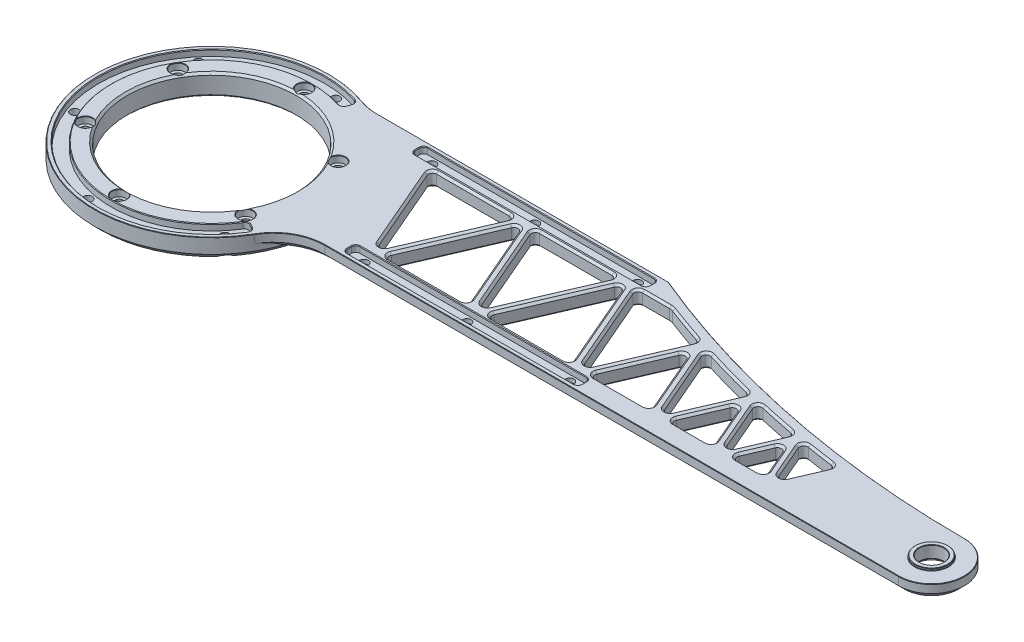
SolidWorks part; units mm, degrees
note: The reader was unsure of these and kept them because the rebuilt part matched: shared geometry of "스케치1<37>", "스케치1<38>".
material "6061-T6 (SS)"
ref_plane "정면" through (0, 0, 0) normal (0, 0, 1) x (1, 0, 0)
ref_plane "윗면" through (0, 0, 0) normal (0, 1, 0) x (1, 0, 0)
ref_plane "우측면" through (0, 0, 0) normal (1, 0, 0) x (0, 0, -1)
sketch "스케치1" plane through (0, 0, 0) normal (0, 1, 0) x (1, 0, 0)
  line L0 (0, 0) -> (350, 0) construction
  line L1 (0, 45) -> (0, 0) construction
  line L2 (0, 0) -> (38.9711, 22.5) construction
  line L3 (71.0141, -16) -> (350, -16)
  line L4 (350, -14) -> (71.0141, -14)
  line L5 (350, 32) -> (350, 40) construction
  line L6 (350, 16) -> (46.3141, 16) construction
  line L7 (350, 40) -> (40.6079, 40) construction
  line L8 (169.6004, 50) -> (28.1957, 50)
  line L9 (170, 52) -> (28.1957, 52)
  line L10 (85, -11) -> (185, -11) construction
  line L11 (0, 32) -> (350, 32) construction
  line L12 (0, 45) -> (0, 0) construction
  line L13 (0, 0) -> (-39.8343, 33.425) construction
  line L14 (-39.8343, 33.425) -> (0, 0) construction
  line L15 (0, 0) -> (-52, 0) construction
  line L16 (60, 47) -> (160, 47) construction
  line L17 (-39.8343, 33.425) -> (0, 0) construction
  line L18 (0, 0) -> (9.0297, 51.21) construction
  circle A18 centre (0, 0) radius 41
  circle A19 centre (350, 0) radius 6
  circle A25 centre (0, 0) radius 45
  circle A26 centre (0, 0) radius 49
  circle A28 centre (0, 45) radius 2.1
  circle A33 centre (0, 45) radius 3.5
  circle A34 centre (38.9711, 22.5) radius 2.1
  circle A36 centre (38.9711, 22.5) radius 3.5
  circle A37 centre (38.9711, -22.5) radius 2.1
  circle A38 centre (38.9711, -22.5) radius 3.5
  circle A40 centre (0, -45) radius 2.1
  circle A41 centre (0, -45) radius 3.5
  circle A42 centre (-38.9711, -22.5) radius 2.1
  circle A44 centre (-38.9711, -22.5) radius 3.5
  circle A45 centre (-38.9711, 22.5) radius 2.1
  circle A46 centre (-38.9711, 22.5) radius 3.5
  circle A48 centre (350, 0) radius 14
  arc A49 (322.2872, -16) -> (322.7607, 16.7934) centre (350, 0) ccw
  circle A50 centre (0, 0) radius 32
  arc A52 (350, -16) -> (342.254, -14) centre (350, 0) ccw
  arc A60 (170, 52) -> (350, 16) centre (350, 484) ccw
  arc A61 (169.6004, 50) -> (350, 14) centre (350, 484) ccw
  arc A75 (19.5995, 53.5244) -> (49.3634, -28.5) centre (0, 0) ccw
  arc A110 (71.0141, -16) -> (49.3634, -28.5) centre (71.0141, -41) ccw
  arc A111 (71.0141, -14) -> (47.6314, -27.5) centre (71.0141, -41) ccw
  circle A114 centre (0, 0) radius 55
  circle A130 centre (0, 0) radius 52
  circle A131 centre (60, 47) radius 2.1
  circle A142 centre (-39.8343, 33.425) radius 2.1
  circle A143 centre (9.0297, 51.21) radius 2.1
  circle A145 centre (39.8343, -33.425) radius 2.1
  circle A146 centre (-9.0297, -51.21) radius 2.1
  arc A147 (19.5995, 53.5244) -> (28.1957, 52) centre (28.1957, 77) ccw
  arc A148 (18.9118, 51.6463) -> (28.1957, 50) centre (28.1957, 77) ccw
  arc A149 (53.0537, -20.84) -> (27.3679, 50) centre (0, 0) ccw
  circle A152 centre (85, -11) radius 2.1
  circle A161 centre (135, -11) radius 2.1
  circle A165 centre (185, -11) radius 2.1
  circle A168 centre (110, 47) radius 2.1
  circle A172 centre (235, -11) radius 2.1 [skipped]
  circle A177 centre (160, 47) radius 2.1
  circle A180 centre (0, 0) radius 57
  circle A181 centre (-48.864, -17.785) radius 2.1
  circle A182 centre (48.864, 17.785) radius 2.1 [skipped]
  point P29 (0, 0)
  point P57 (-0.5, 0.2887)
  point P59 (0, 0)
  point P73 (0, 0)
  point P120 (0, 0)
  point P168 (0, 0)
  point P170 (0, 0)
  point P171 (0, 0)
  dimension "D2" = 82
  dimension "D3" = 90
  dimension "D4" = 98
  dimension "D7" = 7
  dimension "D8" = 60
  dimension "D10" = 28
  dimension "D11" = 64
  dimension "D12" = 64
  dimension "D13" = 32
  dimension "D14" = 60
  dimension "D19" = 50
  dimension "D21" = 50
  dimension "D17" = 180
  dimension "D20" = 3
  dimension "D22" = 8
  dimension "D23" = 2
  dimension "D25" = 50
  dimension "D26" = 4.2
  dimension "D28" = 85
  dimension "D32" = 3
  dimension "D33" = 50
  dimension "D35" = 4
  dimension "D5" = 114
  dimension "D6" = 4.2
  dimension "D9" = 12
  dimension "D18" = 6
  dimension "D16" = 104
  dimension "D27" = 4.2
  dimension "D37" = 25
  dimension "D15" = 4.2
  dimension "D1" = 350
  dimension "D34" = 6
  dimension "D38" = 50
  dimension "D24" = 10
  dimension "D30" = 3
sketch "스케치2" plane through (0, 0, 0) normal (0, 1, 0) x (1, 0, 0)
  circle A10 centre (350, 0) radius 6.25
  circle A11 centre (382.6753, 12.5429) radius 10
  arc A12 (390.9123, -1.174) -> (378.5037, 27.9895) centre (382.6753, 12.5429) ccw
  arc A13 (231.9844, -40.1605) -> (80.8156, -91.5048) centre (227.4834, -275.1173) ccw
  arc A14 (357.0381, -19.254) -> (358.9138, -18.4606) centre (350, 0) ccw
  arc A15 (358.9138, -18.4606) -> (390.9123, -1.174) centre (184.9867, 341.7468) ccw
  arc A16 (231.9844, -40.1605) -> (357.0381, -19.254) centre (238.5923, 304.7763) ccw
  arc A17 (378.5037, 27.9895) -> (343.7427, 16.8774) centre (482.7931, -358.1759) ccw
  arc A18 (233.0814, -9.5331) -> (343.3893, 16.7421) centre (196.4849, 388.7893) ccw
  arc A19 (233.0814, -9.5331) -> (41.3157, -82.3545) centre (261.5552, -373.4208) ccw
sketch "스케치3" plane through (0, 0, 0) normal (0, 1, 0) x (1, 0, 0)
  line L0 (350, -2.1721) -> (350, 87.1857) construction
  line L1 (350, 32) -> (0, 32) construction
  line L2 (350, 36) -> (-50.8808, 36) construction
  line L3 (350, 28) -> (-10.04, 28) construction
  circle A0 centre (356.8277, -1.9267) radius 6.25
  circle A1 centre (350, 32) radius 10
  arc A2 (365.7576, 37.7743) -> (333.8887, 36.6981) centre (350, 32) ccw
  arc A3 (345.2, -124.5693) -> (338.96, -284.0977) centre (562.9381, -212.9724) ccw
  arc A4 (377.1409, -4.6879) -> (376.6334, 3.3632) centre (356.8277, -1.9267) ccw
  arc A5 (376.6334, 3.3632) -> (365.7576, 37.7743) centre (-9.8202, -99.853) ccw
  arc A6 (345.2, -124.5693) -> (377.1409, -4.6879) centre (-114.7569, 62.1762) ccw
  arc A7 (333.8887, 36.6981) -> (325.3353, 1.5106) centre (717.8951, -75.28) ccw
  arc A8 (317, -112.5693) -> (332.0008, -0.1718) centre (-67.981, -3.9891) ccw
  arc A9 (317, -112.5693) -> (316.262, -317.6949) centre (666.9225, -216.3924) ccw
  dimension "D1" = 4
  dimension "D2" = 4
extrude "보스-돌출1" add sketch "스케치1" along normal blind 7
extrude "보스-돌출2" add sketch "스케치1<37>" against normal blind 3.2
sketch "스케치1<37>" plane through (0, 0, 0) normal (0, 1, 0) x (1, 0, 0) same geometry as "스케치1"
extrude "컷-돌출1" cut sketch "스케치1<38>" against normal blind 3.2 from surface at 7 contours A25 A33 A28 | A25 A33 A28 | A25 A46 A45 | A25 A46 A45 | A25 A44 A42 | A25 A44 A42 | A25 A41 A40 | A25 A41 A40 | A25 A38 A37 | A25 A38 A37 | A25 A36 A34 | A25 A36 A34
sketch "스케치1<38>" plane through (0, 0, 0) normal (0, 1, 0) x (1, 0, 0) same geometry as "스케치1"
sketch "스케치5" plane through (0, -3.2, 0) normal (0, -1, 0) x (1, 0, 0)
  line L0 (-9.0297, 51.21) -> (0, 0) construction
  line L1 (0, 0) -> (39.8343, 33.425) construction
  circle A0 centre (-9.0297, 51.21) radius 3.5
  circle A1 centre (39.8343, 33.425) radius 3.5
  circle A3 centre (9.0297, -51.21) radius 3.5
  circle A4 centre (-39.8343, -33.425) radius 3.5
  circle A5 centre (-48.864, 17.785) radius 3.5
  circle A6 centre (48.864, -17.785) radius 3.5 [skipped]
  point P15 (0, 0)
  dimension "D1" = 7
  dimension "D3" = 60
  dimension "D2" = 6
extrude "컷-돌출2" cut sketch "스케치5" against normal blind 3.2
sketch "스케치4" plane through (0, 7, 0) normal (0, 1, 0) x (1, 0, 0)
  line L0 (0, 0) -> (19.5995, 53.5244) construction
  line L1 (16.8487, 46.0122) -> (18.9118, 51.6463)
  line L2 (0, 0) -> (49.3634, -28.5) construction
  line L3 (47.6314, -27.5) -> (42.4352, -24.5)
  line L4 (55, 44) -> (165, 44)
  line L5 (55, 50) -> (165, 50)
  line L6 (53, 48) -> (53, 46)
  line L7 (167, 48) -> (167, 46)
  line L8 (80, -8) -> (190, -8)
  line L9 (80, -14) -> (190, -14)
  line L10 (78, -10) -> (78, -12)
  line L11 (192, -10) -> (192, -12)
  line L12 (60, 47) -> (160, 47) construction
  line L13 (85, -11) -> (185, -11) construction
  circle A0 centre (0, 0) radius 52
  circle A1 centre (0, 0) radius 55
  circle A2 centre (0, 0) radius 49
  arc A29 (46.5597, -29.2778) -> (45.8667, -26.4811) centre (44.8667, -28.2132) ccw
  arc A32 (44.1333, -25.4804) -> (41.4418, -26.1453) centre (43.1333, -27.2124) ccw
  arc A33 (18.2111, 49.7328) -> (16.9494, 52.3232) centre (16.333, 50.4205) ccw
  arc A34 (15.0313, 46.6375) -> (17.5229, 47.8534) centre (15.6448, 48.5411) ccw
  arc A35 (165, 44) -> (167, 46) centre (165, 46) ccw
  arc A36 (165, 50) -> (167, 48) centre (165, 48) cw
  arc A37 (55, 44) -> (53, 46) centre (55, 46) cw
  arc A38 (55, 50) -> (53, 48) centre (55, 48) ccw
  arc A40 (190, -14) -> (192, -12) centre (190, -12) ccw
  arc A41 (190, -8) -> (192, -10) centre (190, -10) cw
  arc A42 (80, -14) -> (78, -12) centre (80, -12) cw
  arc A43 (80, -8) -> (78, -10) centre (80, -10) ccw
  circle M26 centre (39.8343, -33.425) radius 2.1
  circle M27 centre (-9.0297, -51.21) radius 2.1
  circle M28 centre (-48.864, -17.785) radius 2.1
  circle M29 centre (-39.8343, 33.425) radius 2.1
  circle M30 centre (185, -11) radius 2.1
  circle M31 centre (135, -11) radius 2.1
  circle M32 centre (85, -11) radius 2.1
  circle M40 centre (60, 47) radius 2.1
  circle M41 centre (110, 47) radius 2.1
  circle M42 centre (160, 47) radius 2.1
  dimension "D9" = 2
  dimension "D10" = 3
  dimension "D13" = 7
  dimension "D2" = 3
  dimension "D3" = 3
  dimension "D4" = 2
  dimension "D5" = 2
  dimension "D14" = 2
  dimension "D1" = 3
  dimension "D6" = 3
  dimension "D7" = 7
  dimension "D8" = 7
  dimension "D11" = 3
  dimension "D12" = 7
extrude "컷-돌출3" cut sketch "스케치4" against normal blind 3 contours L1 A33 A1 A29 L3 A0 M26 M27 M28 M29 | A2 A34 L1 A0 L3 A32 M29 M28 M27 M26 | L5 A38 L6 A37 L4 A35 L7 A36 M41 M40 M42 | L8 A43 L10 A42 L9 A40 L11 A41 M31 M32 M30
sketch "스케치6" plane through (0, 7, 0) normal (0, 1, 0) x (1, 0, 0)
  circle A0 centre (350, 0) radius 6
  circle A1 centre (350, 0) radius 8
  dimension "D1" = 12
  dimension "D2" = 16
extrude "보스-돌출3" add sketch "스케치6" along normal blind 1
sketch "스케치7" plane through (0, 0, 0) normal (0, -1, 0) x (1, 0, 0)
  circle A0 centre (85, 11) radius 3.5
  circle A1 centre (135, 11) radius 3.5
  circle A2 centre (185, 11) radius 3.5
  circle A3 centre (160, -47) radius 3.5
  circle A4 centre (110, -47) radius 3.5
  circle A5 centre (60, -47) radius 3.5
  dimension "D1" = 7
extrude "컷-돌출4" cut sketch "스케치7" against normal blind 2
sketch "스케치8" plane through (0, 7, 0) normal (0, 1, 0) x (1, 0, 0)
  line L0 (60, 47) -> (85, -11) construction
  line L1 (85, -11) -> (110, 47) construction
  line L2 (110, 47) -> (135, -11) construction
  line L3 (135, -11) -> (160, 47) construction
  line L4 (160, 47) -> (185, -11) construction
  line L5 (92.373, -6) -> (127.627, -6)
  line L6 (185, -11) -> (204.3845, 33.9721) construction
  line L7 (204.3845, 33.9721) -> (223.769, -11) construction
  line L8 (223.769, -11) -> (238.9504, 24.2207) construction
  line L9 (238.9504, 24.2207) -> (254.1317, -11) construction
  line L10 (254.1317, -11) -> (266.7938, 18.376) construction
  line L11 (65.5364, 39.2083) -> (83.1634, -1.6863)
  line L12 (67.373, 42) -> (102.627, 42)
  line L13 (104.4636, 39.2083) -> (86.8366, -1.6863)
  line L14 (55, 44) -> (165, 44) construction
  line L15 (108.1634, 37.6863) -> (90.5364, -3.2083)
  line L16 (111.8366, 37.6863) -> (129.4636, -3.2083)
  line L17 (80, -8) -> (190, -8) construction
  line L18 (115.5364, 39.2083) -> (133.1634, -1.6863)
  line L19 (117.373, 42) -> (152.627, 42)
  line L20 (154.4636, 39.2083) -> (136.8366, -1.6863)
  line L21 (55, 44) -> (165, 44) construction
  line L22 (158.1634, 37.6863) -> (140.5364, -3.2083)
  line L23 (161.8366, 37.6863) -> (179.4636, -3.2083)
  line L24 (142.373, -6) -> (177.627, -6)
  line L25 (231.142, -6) -> (246.7587, -6)
  line L26 (237.1137, 14.907) -> (229.3054, -3.2083)
  line L27 (165.5364, 39.2083) -> (183.1634, -1.6863)
  line L28 (201.6108, 32.5897) -> (186.8366, -1.6863)
  line L29 (192.373, -6) -> (216.396, -6)
  line L30 (202.5479, 24.6584) -> (190.5364, -3.2083)
  line L31 (206.2212, 24.6584) -> (218.2327, -3.2083)
  line L32 (240.787, 14.907) -> (248.5954, -3.2083)
  line L33 (242.9438, 20.0088) -> (252.2951, -1.6863)
  line L34 (208.6351, 29.1633) -> (221.9324, -1.6863)
  line L35 (236.0469, 22.5374) -> (225.6057, -1.6863)
  line L36 (263.782, 16.4414) -> (255.9684, -1.6863)
  line L37 (152.627, 42) -> (180.6631, 42) construction
  line L38 (180.6631, 42) -> (167.373, 42)
  line L39 (266.7938, 18.376) -> (279.4558, -11) construction
  line L40 (279.4558, -11) -> (290.5551, 14.7503) construction
  line L41 (261.5047, -6) -> (272.0828, -6)
  line L42 (264.9571, 9.0623) -> (259.6681, -3.2083)
  line L43 (268.6304, 9.0623) -> (273.9195, -3.2083)
  line L44 (270.6067, 14.5827) -> (277.6192, -1.6863)
  line L45 (287.4473, 12.5928) -> (281.2925, -1.6863)
  circle A0 centre (350, 484) radius 468
  arc A1 (170, 52) -> (350, 16) centre (350, 484) ccw construction
  circle A2 centre (350, 484) radius 473
  arc A7 (83.1634, -1.6863) -> (86.8366, -1.6863) centre (85, -0.8946) ccw
  arc A8 (104.4636, 39.2083) -> (102.627, 42) centre (102.627, 40) ccw
  arc A9 (65.5364, 39.2083) -> (67.373, 42) centre (67.373, 40) cw
  arc A10 (92.373, -6) -> (90.5364, -3.2083) centre (92.373, -4) cw
  arc A11 (127.627, -6) -> (129.4636, -3.2083) centre (127.627, -4) ccw
  arc A12 (111.8366, 37.6863) -> (108.1634, 37.6863) centre (110, 36.8946) ccw
  arc A13 (136.8366, -1.6863) -> (133.1634, -1.6863) centre (135, -0.8946) cw
  arc A14 (154.4636, 39.2083) -> (152.627, 42) centre (152.627, 40) ccw
  arc A15 (115.5364, 39.2083) -> (117.373, 42) centre (117.373, 40) cw
  arc A16 (177.627, -6) -> (179.4636, -3.2083) centre (177.627, -4) ccw
  arc A17 (142.373, -6) -> (140.5364, -3.2083) centre (142.373, -4) cw
  arc A18 (161.8366, 37.6863) -> (158.1634, 37.6863) centre (160, 36.8946) ccw
  arc A19 (186.8366, -1.6863) -> (183.1634, -1.6863) centre (185, -0.8946) cw
  arc A20 (201.6108, 32.5897) -> (200.4067, 35.2787) centre (199.7741, 33.3813) ccw
  arc A22 (216.396, -6) -> (218.2327, -3.2083) centre (216.396, -4) ccw
  arc A23 (192.373, -6) -> (190.5364, -3.2083) centre (192.373, -4) cw
  arc A24 (206.2212, 24.6584) -> (202.5479, 24.6584) centre (204.3845, 23.8667) ccw
  arc A25 (225.6057, -1.6863) -> (221.9324, -1.6863) centre (223.769, -0.8946) cw
  arc A26 (211.0593, 31.8668) -> (208.6351, 29.1633) centre (210.4718, 29.955) ccw
  arc A27 (236.0469, 22.5374) -> (234.6978, 25.2687) centre (234.2103, 23.329) ccw
  arc A28 (246.7587, -6) -> (248.5954, -3.2083) centre (246.7587, -4) ccw
  arc A29 (231.142, -6) -> (229.3054, -3.2083) centre (231.142, -4) cw
  arc A30 (240.787, 14.907) -> (237.1137, 14.907) centre (238.9504, 14.1154) ccw
  arc A31 (255.9684, -1.6863) -> (252.2951, -1.6863) centre (254.1317, -0.8946) cw
  arc A32 (245.2234, 22.7507) -> (242.9438, 20.0088) centre (244.7804, 20.8004) ccw
  arc A33 (263.782, 16.4414) -> (262.3161, 19.1984) centre (261.9454, 17.2331) ccw
  arc A34 (165.5364, 39.2083) -> (167.373, 42) centre (167.373, 40) cw
  arc A35 (182.4344, 41.6757) -> (180.6631, 42) centre (180.6631, 37) ccw
  arc A36 (272.0828, -6) -> (273.9195, -3.2083) centre (272.0828, -4) ccw
  arc A37 (261.5047, -6) -> (259.6681, -3.2083) centre (261.5047, -4) cw
  arc A38 (268.6304, 9.0623) -> (264.9571, 9.0623) centre (266.7938, 8.2706) ccw
  arc A39 (281.2925, -1.6863) -> (277.6192, -1.6863) centre (279.4558, -0.8946) cw
  arc A40 (272.7699, 17.3475) -> (270.6067, 14.5827) centre (272.4433, 15.3744) ccw
  arc A41 (287.4473, 12.5928) -> (285.8817, 15.366) centre (285.6106, 13.3844) ccw
  dimension "D1" = 5
  dimension "D5" = 2
  dimension "D9" = 2
  dimension "D13" = 2
  dimension "D16" = 2
  dimension "D19" = 2
  dimension "D20" = 4
  dimension "D21" = 2
  dimension "D24" = 2
  dimension "D27" = 2
  dimension "D28" = 4
  dimension "D31" = 2
  dimension "D34" = 2
  dimension "D35" = 4
  dimension "D36" = 10
  dimension "D39" = 2
  dimension "D42" = 2
  dimension "D43" = 4
  dimension "D2" = 2
  dimension "D3" = 2
  dimension "D4" = 2
  dimension "D6" = 2
  dimension "D7" = 2
  dimension "D8" = 2
  dimension "D10" = 2
  dimension "D11" = 2
  dimension "D12" = 2
  dimension "D14" = 2
  dimension "D15" = 2
  dimension "D17" = 2
  dimension "D18" = 2
  dimension "D22" = 2
  dimension "D23" = 2
  dimension "D25" = 2
  dimension "D26" = 2
  dimension "D29" = 2
  dimension "D30" = 2
  dimension "D32" = 2
  dimension "D33" = 2
  dimension "D37" = 2
  dimension "D38" = 2
  dimension "D40" = 2
  dimension "D41" = 2
extrude "컷-돌출5" cut sketch "스케치8" against normal blind 7 contours A9 L11 A7 L13 A8 L12 | L16 A12 L15 A10 L5 A11 | A15 L18 A13 L20 A14 L19 | L23 A18 L22 A17 L24 A16 | A2 A35 L38 A34 L27 A19 L28 A20 | L31 A24 L30 A23 L29 A22 | L35 A27 A2 A26 L34 A25 | L32 A30 L26 A29 L25 A28 | L36 A33 A2 A32 L33 A31 | L43 A38 L42 A37 L41 A36 | L45 A41 A2 A40 L44 A39
chamfer "모따기1" distance 3 angle 45 1 edges at (0, -3.2, 57)
chamfer "모따기3" distance 3 angle 45 6 edges at (23.8306, 0, -52.384) (58.5141, 0, 19.3494) (99.0979, 0, -52) (258.2176, 0, -25.0882) (366, 0, 0) (210.507, 0, 16)
sketch "스케치9" plane through (0, 0, 0) normal (0, -1, 0) x (1, 0, 0)
  circle A0 centre (350, 0) radius 8
  dimension "D1" = 16
extrude "컷-돌출6" cut sketch "스케치9" against normal blind 2
chamfer "모따기4" distance 0.3 angle 45 26 edges at (53.5858, 7, -44.5858) (53, 7, -47) (53.5858, 7, -49.4142) (110, 7, -44) (110, 7, -50) (166.4142, 7, -44.5858) (167, 7, -47) (166.4142, 7, -49.4142) (191.4142, 7, 13.4142) (192, 7, 11) (191.4142, 7, 8.5858) (135, 7, 8) (78.5858, 7, 8.5858) (78, 7, 11) (78.5858, 7, 13.4142) (135, 7, 14) (46.8079, 7, 27.7321) (45, 7, 25.9808) (42.6537, 7, 25.2708) (-46.0612, 7, 16.7141) (16.522, 7, -46.7437) (17.867, 7, -48.7931) (18.1311, 7, -51.2963) (-51.7014, 7, 18.7607) (350, 0, -8) (350, 2, -6)
chamfer "모따기5" distance 0.2 angle 45 27 edges at (-45.5751, -3.2, 16.588) (-37.1532, -3.2, -31.1752) (8.4219, -3.2, -47.7632) (-8.4219, -3.2, 47.7632) (37.1532, -3.2, 31.1752) (185, 0, 7.5) (135, 0, 7.5) (85, 0, 7.5) (60, 0, -43.5) (110, 0, -43.5) (160, 0, -43.5) (38.9711, 7, 26) (0, 7, 48.5) (-38.9711, 7, 26) (-38.9711, 7, -19) (38.9711, 7, -19) (0, 7, -41.5) (58.5141, 7, 19.3494) (210.507, 7, 16) (366, 7, 0) (258.2176, 7, -25.0882) (99.0979, 7, -52) (23.8306, 7, -52.384) (-53.5814, 7, 19.443) (350, 8, 6) (350, 8, 8) (350, 7, 8)
chamfer "모따기6" distance 1 angle 45 138 edges at (266.7938, 7, 6) (266.7938, 0, 6) (259.8339, 7, 5.0992) (259.8339, 0, 5.0992) (262.3126, 7, -2.927) (262.3126, 0, -2.927) (266.7938, 7, -10.2706) (266.7938, 0, -10.2706) (271.275, 7, -2.927) (271.275, 0, -2.927) (273.7537, 7, 5.0992) (273.7537, 0, 5.0992) (279.4558, 7, 2.8946) (279.4558, 0, 2.8946) (274.1129, 7, -6.4482) (274.1129, 0, -6.4482) (284.3699, 7, -5.4532) (284.3699, 0, -5.4532) (287.3523, 7, -14.3676) (287.3523, 0, -14.3676) (270.8682, 7, -16.6068) (270.8682, 0, -16.6068) (279.3189, 7, -16.3108) (279.3189, 0, -16.3108) (243.2425, 7, -22.079) (243.2425, 0, -22.079) (253.7534, 7, -20.8957) (253.7534, 0, -20.8957) (263.7113, 7, -18.172) (263.7113, 0, -18.172) (259.8752, 7, -7.3775) (259.8752, 0, -7.3775) (247.6194, 7, -9.1612) (247.6194, 0, -9.1612) (254.1317, 7, 2.8946) (254.1317, 0, 2.8946) (229.4712, 7, 5.0992) (229.4712, 0, 5.0992) (238.9504, 7, 6) (238.9504, 0, 6) (248.4296, 7, 5.0992) (248.4296, 0, 5.0992) (233.2096, 7, -5.8493) (233.2096, 0, -5.8493) (244.6912, 7, -5.8493) (244.6912, 0, -5.8493) (238.9504, 7, -16.1154) (238.9504, 0, -16.1154) (208.9827, 7, -31.2902) (208.9827, 0, -31.2902) (222.8357, 7, -28.4144) (222.8357, 0, -28.4144) (236.0034, 7, -24.2148) (236.0034, 0, -24.2148) (230.8263, 7, -10.4255) (230.8263, 0, -10.4255) (215.2838, 7, -13.7385) (215.2838, 0, -13.7385) (223.769, 7, 2.8946) (223.769, 0, 2.8946) (204.3845, 7, 6) (204.3845, 0, 6) (190.7022, 7, 5.0992) (190.7022, 0, 5.0992) (218.0669, 7, 5.0992) (218.0669, 0, 5.0992) (196.5421, 7, -10.725) (196.5421, 0, -10.725) (212.2269, 7, -10.725) (212.2269, 0, -10.725) (204.3845, 7, -25.8667) (204.3845, 0, -25.8667) (160, 7, 6) (160, 0, 6) (140.7022, 7, 5.0992) (140.7022, 0, 5.0992) (179.2978, 7, 5.0992) (179.2978, 0, 5.0992) (149.3499, 7, -17.239) (149.3499, 0, -17.239) (170.6501, 7, -17.239) (170.6501, 0, -17.239) (160, 7, -38.8946) (160, 0, -38.8946) (185, 7, 2.8946) (185, 0, 2.8946) (174.3499, 7, -18.761) (174.3499, 0, -18.761) (194.2237, 7, -15.4517) (194.2237, 0, -15.4517) (201.5995, 7, -34.1987) (201.5995, 0, -34.1987) (191.3883, 7, -38.3866) (191.3883, 0, -38.3866) (181.5634, 7, -41.9183) (181.5634, 0, -41.9183) (165.7022, 7, -41.0992) (165.7022, 0, -41.0992) (174.018, 7, -42) (174.018, 0, -42) (115.7022, 7, -41.0992) (115.7022, 0, -41.0992) (135, 7, -42) (135, 0, -42) (154.2978, 7, -41.0992) (154.2978, 0, -41.0992) (145.6501, 7, -18.761) (145.6501, 0, -18.761) (124.3499, 7, -18.761) (124.3499, 0, -18.761) (135, 7, 2.8946) (135, 0, 2.8946) (129.2978, 7, 5.0992) (129.2978, 0, 5.0992) (110, 7, 6) (110, 0, 6) (90.7022, 7, 5.0992) (90.7022, 0, 5.0992) (99.3499, 7, -17.239) (99.3499, 0, -17.239) (120.6501, 7, -17.239) (120.6501, 0, -17.239) (110, 7, -38.8946) (110, 0, -38.8946) (85, 7, 2.8946) (85, 0, 2.8946) (95.6501, 7, -18.761) (95.6501, 0, -18.761) (74.3499, 7, -18.761) (74.3499, 0, -18.761) (65.7022, 7, -41.0992) (65.7022, 0, -41.0992) (104.2978, 7, -41.0992) (104.2978, 0, -41.0992) (85, 7, -42) (85, 0, -42) (0, 7, 41) (0, -3.2, 41)
